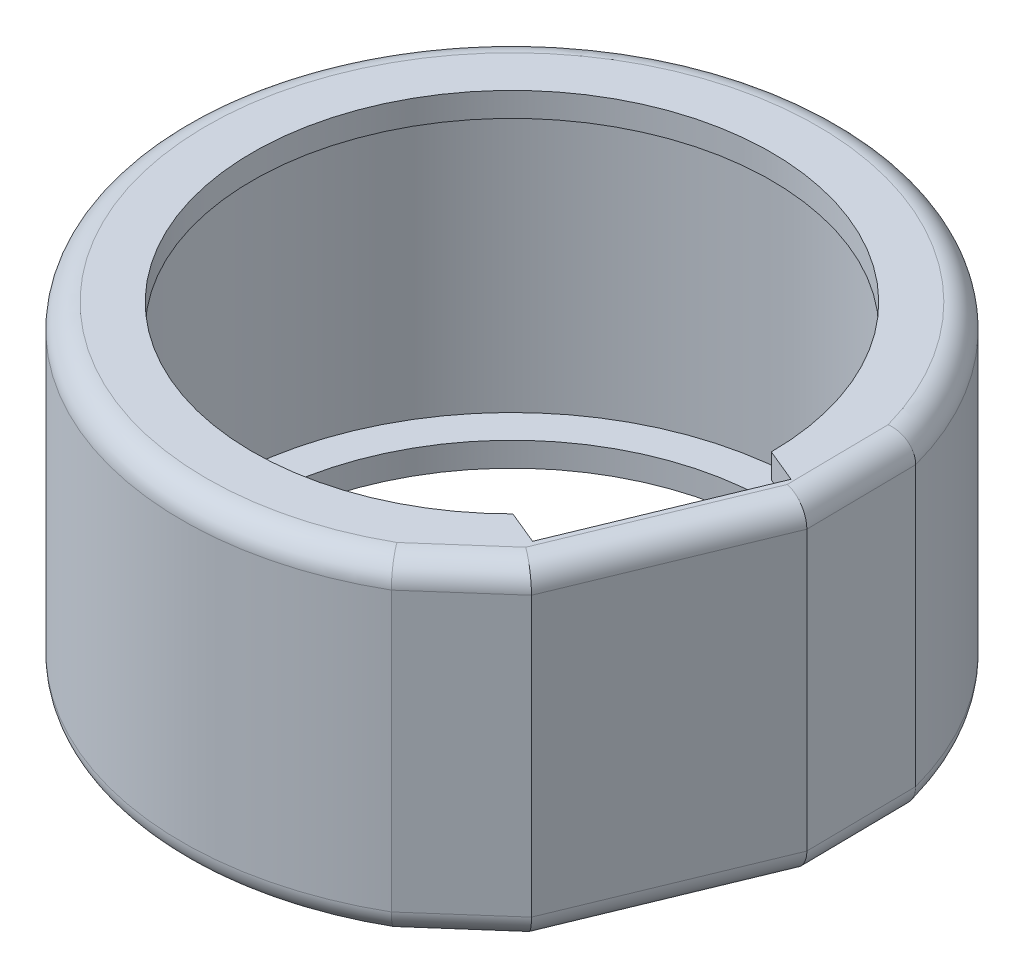
SolidWorks part; units mm, degrees
ref_plane "前视基准面" through (0, 0, 0) normal (0, 0, 1) x (1, 0, 0)
ref_plane "上视基准面" through (0, 0, 0) normal (0, 1, 0) x (1, 0, 0)
ref_plane "右视基准面" through (0, 0, 0) normal (1, 0, 0) x (0, 0, -1)
sketch "草图1" plane through (0, 0, 0) normal (0, 1, 0) x (1, 0, 0)
  line L0 (0, 0) -> (10.7, 0) construction
  line L1 (0, 0) -> (7.5841, -7.5479) construction
  line L6 (0, 0) -> (13.1366, 3.5199) construction
  line L7 (0, 0) -> (6.8, -11.7779) construction
  line L10 (10.7, 0) -> (13.882, -1.3136) construction
  line L20 (13.1957, -1.0303) -> (9.876, -9.072)
  line L21 (13.1957, -1.0303) -> (13.1366, 3.5199)
  line L22 (9.876, -9.072) -> (6.8, -11.7779)
  line L23 (10.7, 0) -> (7.5841, -7.5479)
  arc A0 (10.7, 0) -> (7.5841, -7.5479) centre (0, 0) ccw
  arc A3 (13.1366, 3.5199) -> (6.8, -11.7779) centre (0, 0) ccw
extrude "凸台-拉伸1" add sketch "草图1" along normal blind 1
sketch "草图2" plane through (0, 0, 0) normal (0, -1, 0) x (-1, 0, 0)
  line L5 (0, 0) -> (-6.8, -11.7779) construction
  line L7 (0, 0) -> (-13.1366, 3.5199) construction
  line L9 (-8.9314, -8.1633) -> (-12.0878, -0.5431)
  line L17 (-13.1957, -1.0303) -> (-13.1366, 3.5199)
  line L19 (-13.1957, -1.0303) -> (-9.876, -9.072)
  line L20 (-9.876, -9.072) -> (-6.8, -11.7779)
  arc A0 (-6.8, -11.7779) -> (-13.1366, 3.5199) centre (0, 0) ccw
  arc A1 (-8.9314, -8.1633) -> (-12.0878, -0.5431) centre (0, 0) ccw
  dimension "D1" = 12.1
  dimension "D2" = 13.6
extrude "凸台-拉伸3" add sketch "草图2" along normal blind 11.5
sketch "草图5" plane through (0, -11.5, 0) normal (0, -1, 0) x (-1, 0, 0)
  line L4 (0, 0) -> (-6.8, -11.7779) construction
  line L5 (0, 0) -> (-13.1366, 3.5199) construction
  line L14 (-13.1366, 3.5199) -> (-13.1957, -1.0303)
  line L19 (-9.876, -9.072) -> (-6.8, -11.7779)
  line L20 (-13.1957, -1.0303) -> (-9.876, -9.072)
  line L21 (-10.7, 0) -> (-7.5841, -7.5479) construction
  line L22 (-10.7, 0) -> (-7.5841, -7.5479)
  arc A1 (-6.8, -11.7779) -> (-13.1366, 3.5199) centre (0, 0) ccw
  arc A2 (-7.5841, -7.5479) -> (-10.7, 0) centre (0, 0) ccw construction
  arc A3 (-7.5841, -7.5479) -> (-10.7, 0) centre (0, 0) ccw
extrude "凸台-拉伸4" add sketch "草图5" along normal blind 1
fillet "圆角1" radius 1 4 edges at (13.1661, -12.5, -1.2448) (-12.5648, -12.5, -5.2045) (8.338, -12.5, 10.425) (11.5358, -12.5, 5.0511) type face fillet first side face at (13.1661, -5.75, -1.2448) first side face at (11.5358, -5.75, 5.0511) first side face at (8.338, -5.75, 10.425) first side face at (-1.2982, -5.75, -0.5377) second side face at (5.1188, -12.5, 2.2567)
fillet "圆角2" radius 1 4 edges at (13.1661, 1, -1.2448) (-12.5648, 1, -5.2045) (8.338, 1, 10.425) (11.5358, 1, 5.0511) type face fillet first side face at (13.1661, -5.25, -1.2448) first side face at (11.5358, -5.25, 5.0511) first side face at (8.338, -5.25, 10.425) first side face at (-1.2982, -5.25, -0.5377) second side face at (-0.3742, 1, -0.1545)
sketch "草图7" plane through (9.1421, 0, 3.774) normal (-0.9243, 0, -0.3816) x (-0.3816, 0, 0.9243)
  line L4 (-4.0829, 1) -> (-4.0829, 0) construction
  line L5 (-4.0829, 1) -> (-4.0829, 0)
  line L6 (-4.0829, 1) -> (4.0829, 1) construction
  line L7 (-4.0829, 1) -> (4.0829, 1)
  line L9 (-4.0829, 0) -> (4.0829, 0)
  line L10 (-4.0829, 0) -> (-4.0829, 1)
  line L11 (-4.0829, 1) -> (4.0829, 1)
  line L12 (4.0829, 0) -> (4.0829, 1)
extrude "切除-拉伸1" cut sketch "草图7" against normal blind 1.5 contours L9 L12 L7 L5
sketch3d "3DSketch1"
  line L0 (-12.7594, 0, 4.7072) -> (-12.7594, -11.5, 4.7072) construction
  line L1 (-11.2081, 0, 7.7031) -> (-11.2081, -11.5, 7.7031) construction
  spline S0 degree 1 poles (-12.7594, 1999.9934, 4.7072) (-12.7594, -2011.4808, 4.7072) knots -173.912465 -173.912465 174.91137 174.91137 only from (-12.7594, 0, 4.7072) to (-12.7594, -11.5, 4.7072) construction
  spline S1 degree 1 poles (-12.7594, 0, 4.7072) (-12.7594, -11.5, 4.7072) knots 0 0 1 1 construction
  spline S2 degree 1 poles (-11.2081, 1999.9934, 7.7031) (-11.2081, -2011.4808, 7.7031) knots -173.912465 -173.912465 174.91137 174.91137 only from (-11.2081, 0, 7.7031) to (-11.2081, -11.5, 7.7031) construction
  spline S3 degree 1 poles (-11.2081, 0, 7.7031) (-11.2081, -11.5, 7.7031) knots 0 0 1 1 construction
  point P2 (-12.7594, 0, 4.7072)
  point P3 (-12.7594, -5.75, 4.7072)
  point P6 (-11.2081, -5.75, 7.7031)
ref_plane "Plane2" through (-11.2081, -5.75, 7.7031) normal (-0.8241, 0, 0.5664) x (0.5664, 0, 0.8241)
sketch "Sketch5" plane through (-11.2081, -5.75, 7.7031) normal (-0.8241, 0, 0.5664) x (0.5664, 0, 0.8241)
  circle A1 centre (0, 0) radius 0.8
extrude "Cut-Extrude1" cut sketch "Sketch5" against normal up to surface (1.5265 mm away) up to face at (-0.3347, -5.75, -0.1386)
